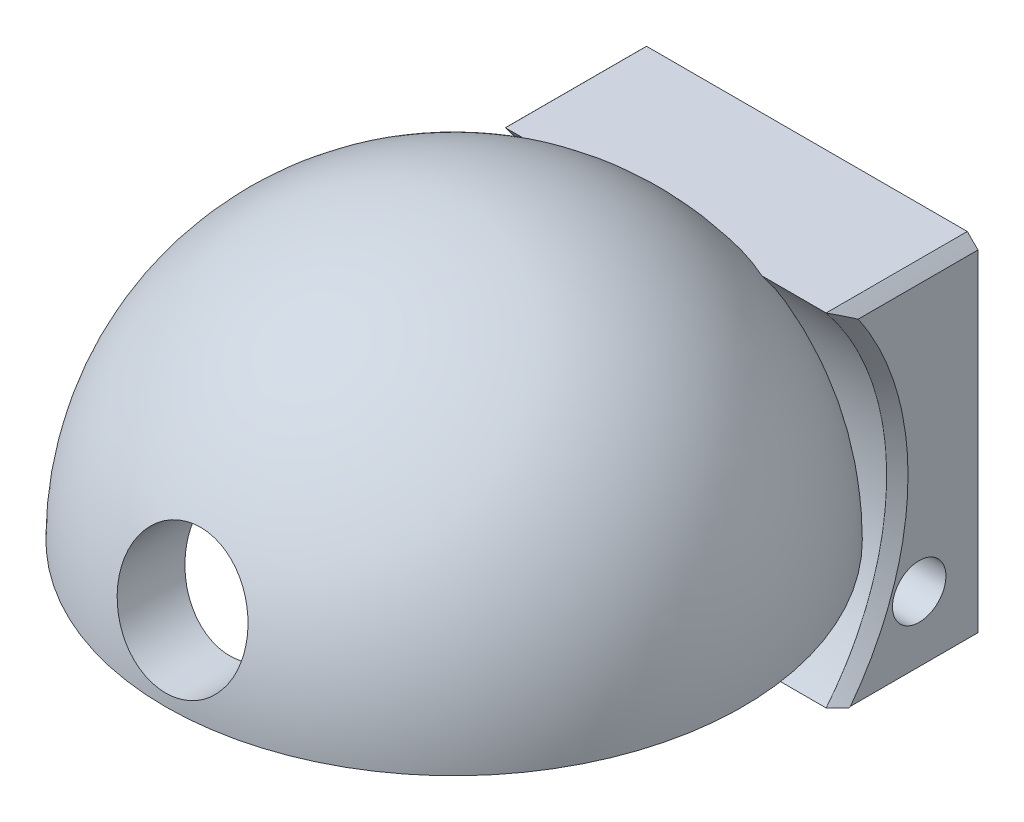
SolidWorks part; units mm, degrees
ref_plane "Front Plane" through (0, 0, 0) normal (0, 0, 1) x (1, 0, 0)
ref_plane "Top Plane" through (0, 0, 0) normal (0, 1, 0) x (1, 0, 0)
ref_plane "Right Plane" through (0, 0, 0) normal (1, 0, 0) x (0, 0, -1)
ref_plane "Plane1" through (-3.25, 0, 0) normal (-1, 0, 0) x (0, 0, 1)
sketch "Sketch2" plane through (-3.25, 0, 0) normal (-1, 0, 0) x (0, 0, 1)
  line L0 (-1.628, 8.4513) -> (-4.628, 8.4513) construction
  line L5 (11.872, 18.9513) -> (11.872, 21.9513)
  line L6 (1.372, 8.4513) -> (-1.628, 8.4513)
  line L7 (11.872, 21.9513) -> (11.872, 8.4513) construction
  arc A0 (11.872, 21.9513) -> (-1.628, 8.4513) centre (11.872, 8.4513) ccw
  arc A3 (11.872, 18.9513) -> (1.372, 8.4513) centre (11.872, 8.4513) ccw
  arc A4 (1.372, 8.4513) -> (5.0713, 0.4513) centre (11.872, 8.4513) ccw construction
  arc A5 (1.372, 8.4513) -> (5.0713, 0.4513) centre (11.872, 8.4513) ccw construction
  dimension "D1" = 3
revolve "Revolve1" add sketch "Sketch2" angle 360 about L7
sketch "Sketch3" plane through (0, 0, -4.628) normal (0, 0, 1) x (1, 0, 0)
  line L0 (-7.75, 8.4513) -> (1.25, 8.4513) construction
  line L1 (-7.75, 8.4513) -> (1.25, 8.4513)
  line L2 (-5.75, 11.9513) -> (-7.75, 11.9513) construction
  line L3 (-3.25, 14.4513) -> (-3.25, 16.4513) construction
  line L4 (-0.75, 11.9513) -> (1.25, 11.9513) construction
  line L5 (-7.75, 8.4513) -> (1.25, 8.4513)
  line L6 (-7.75, 8.4513) -> (-7.75, 16.4513)
  line L7 (-7.75, 16.4513) -> (1.25, 16.4513)
  line L8 (1.25, 8.4513) -> (1.25, 16.4513)
  line L9 (-3.25, 9.4513) -> (-3.25, 8.4513) construction
  circle A0 centre (-3.25, 11.9513) radius 2.5 construction
  circle A2 centre (-3.25, 11.9513) radius 1.25
  circle M11 centre (-42.0626, 3.0448) radius 1.25
  dimension "D1" = 2.5
  dimension "D2" = 5
  dimension "D3" = 1
extrude "Boss-Extrude1" add sketch "Sketch3" along normal up to surface (7.0132 mm away) contours L1 L8 L7 L6 M11 region at (-7.6296, 12.4513, -4.628) up to face at (-13.75, 8.4513, 11.872)
ref_plane "5mmHeadPlane" through (0, 0, -1.628) normal (0, 0, -1) x (-1, 0, 0)
sketch "Sketch4" plane through (0, 0, -1.628) normal (0, 0, 1) x (1, 0, 0)
  circle A4 centre (-3.25, 11.9513) radius 2.95
  circle A5 centre (-3.25, 11.9513) radius 2.95
  dimension "D1" = 1.7
extrude "Cut-Extrude1" cut sketch "Sketch4" along normal through all
sketch "Sketch5" plane through (1.25, 0, 0) normal (1, 0, 0) x (0, 0, -1)
  line L1 (4.628, 16.4513) -> (-1.9725, 16.4513)
  line L2 (4.628, 16.4513) -> (4.628, 0.4513)
  line L3 (4.628, 0.4513) -> (-1.9725, 0.4513)
  line L6 (-1.9725, 0.4513) -> (4.628, 0.4513) construction
  arc A0 (0.8559, 8.4513) -> (-1.9725, 16.4513) centre (-11.872, 8.4513) ccw construction
  arc A1 (0.8559, 8.4513) -> (-1.9725, 16.4513) centre (-11.872, 8.4513) ccw
  arc A2 (-1.9725, 0.4513) -> (0.8559, 8.4513) centre (-11.872, 8.4513) ccw construction
  arc A3 (-1.9725, 0.4513) -> (0.8559, 8.4513) centre (-11.872, 8.4513) ccw
extrude "Boss-Extrude2" add sketch "Sketch5" along normal blind 3.5
fillet "Fillet1" radius 0.5 2 edges at (4.75, 16.4513, -1.3278) (4.75, 8.4513, -0.8559) conic radius 50
mirror "Mirror1" about plane through (-3.25, 0, 0) normal (-1, 0, 0) of "Fillet1", "Boss-Extrude2"
sketch "Sketch6" plane through (4.75, 0, 0) normal (1, 0, 0) x (0, 0, -1)
  line L1 (3.128, 3.4967) -> (4.628, 3.4967) construction
  line L3 (4.628, 0.4513) -> (4.628, 15.9513) construction
  line L4 (-0.872, 0.7467) -> (4.628, 0.7467) construction
  line L5 (-0.872, 0.7467) -> (-0.872, 6.2467) construction
  line L6 (-0.872, 6.2467) -> (4.628, 6.2467) construction
  line L7 (4.628, 0.7467) -> (4.628, 6.2467) construction
  line L8 (1.878, 3.4967) -> (-0.872, 3.4967) construction
  line L9 (1.878, 3.4967) -> (1.878, 6.2467) construction
  circle A0 centre (1.878, 3.4967) radius 1.25
  dimension "D1" = 2.5
  dimension "D2" = 1.5
extrude "Cut-Extrude2" cut sketch "Sketch6" against normal through all
equation "\"D1@Sketch6\"=3-.5"
equation "\"D1@Sketch3\"=3-.5"
equation "\"D1@Sketch4\"=1.50mm+.2"
